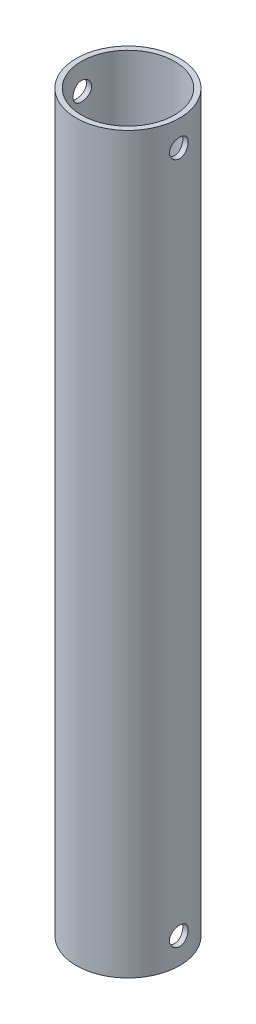
SolidWorks part; units mm, degrees
other "Boss-Extrude"
material "Toray T700"
ref_plane "Front" through (0, 0, 0) normal (0, 0, 1) x (1, 0, 0)
ref_plane "Top" through (0, 0, 0) normal (0, 1, 0) x (1, 0, 0)
ref_plane "Right" through (0, 0, 0) normal (1, 0, 0) x (0, 0, -1)
sketch "Sketch1" plane through (0, 0, 0) normal (0, 1, 0) x (1, 0, 0)
  line L5 (4.7969, 0) -> (-5.97, 0) construction
  circle A0 centre (0, 0) radius 10
  circle A1 centre (0, 0) radius 9
  dimension "D1" = 20
  dimension "D2" = 18
extrude "Boss-Extrude1" add sketch "Sketch1" along normal blind 142
ref_axis "Axis1" through (0, 0, 50) along (0, 0, -1)
ref_axis "Axis3" through (0, 142, 0) along (0, -1, 0)
ref_plane "Plane1" through (10, 0, 0) normal (1, 0, 0) x (0, 0, -1)
ref_plane "Plane2" through (0, 71, 0) normal (0, 1, 0) x (1, 0, 0)
hole_wizard "M3 Clearance Hole1" positions "Sketch5" profile "Sketch6" hole size "M3" standard "DIN" end condition through all
sketch "Sketch5" plane through (10, 0, 0) normal (1, 0, 0) x (0, 0, -1)
  line L0 (-10, 0) -> (10, 0) construction
  point P0 (0, 5)
  dimension "D1" = 5
sketch "Sketch6" plane through (10, 5, 0) normal (0, 1, 0) x (0, 0, -1)
  line L0 (0, 0) -> (0, 20)
  line L1 (0, 20) -> (1.8, 20)
  line L2 (1.8, 20) -> (1.8, 0)
  line L5 (1.8, 0) -> (0, 0)
  line L11 (0, -6.35) -> (0, 107.95) construction
  dimension "Thru Hole Dia." = 3.6
  dimension "Thru Hole Depth" = 20
mirror "Mirror1" about plane through (0, 71, 0) normal (0, 1, 0) of "M3 Clearance Hole1"
